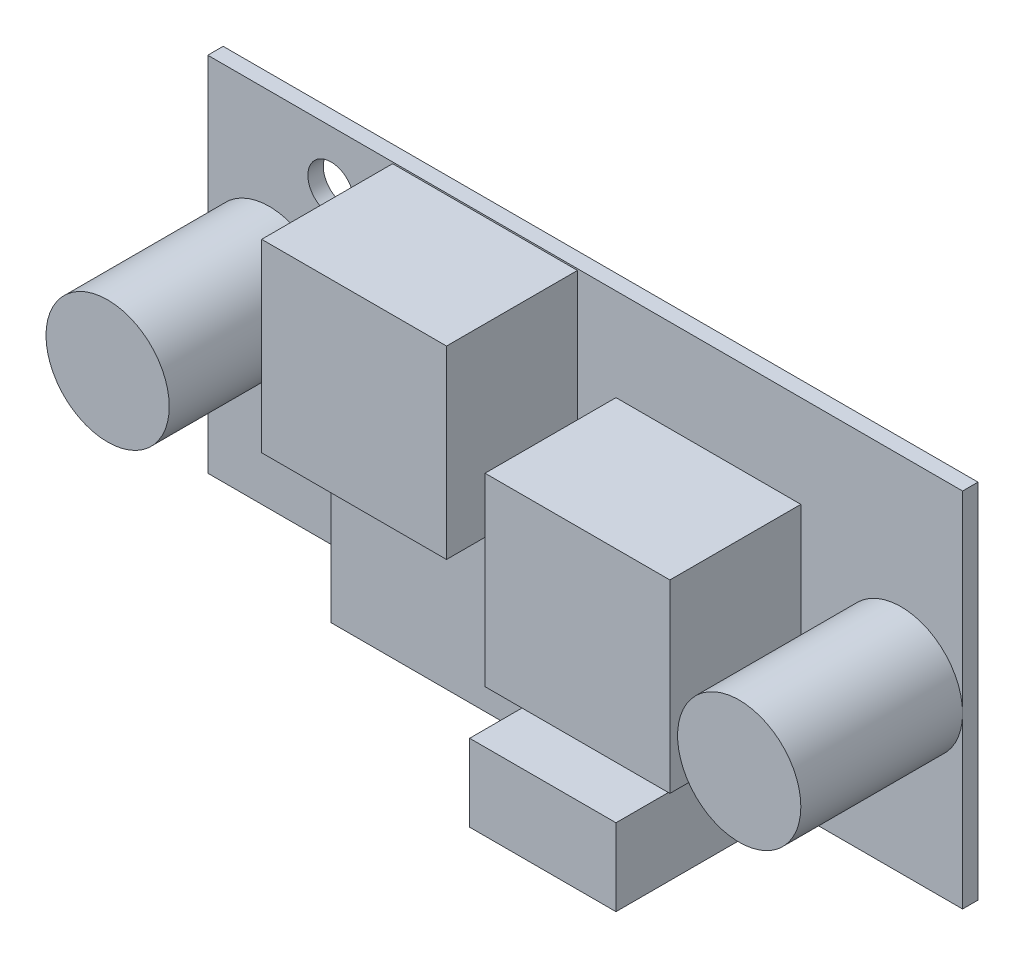
SolidWorks part; units mm, degrees
ref_plane "Спереди" through (0, 0, 0) normal (0, 0, 1) x (1, 0, 0)
ref_plane "Сверху" through (0, 0, 0) normal (0, 1, 0) x (1, 0, 0)
ref_plane "Справа" through (0, 0, 0) normal (1, 0, 0) x (0, 0, -1)
sketch "Эскиз1" plane through (0, 0, 0) normal (0, 0, 1) x (1, 0, 0)
  line L0 (0, 0) -> (-16.5, 8.25) construction
  line L1 (-24.5, 11.75) -> (24.5, 11.75)
  line L2 (-24.5, 11.75) -> (-24.5, -11.75)
  line L3 (-24.5, -11.75) -> (24.5, -11.75)
  line L4 (24.5, 11.75) -> (24.5, -11.75)
  line L5 (-24.5, 11.75) -> (24.5, -11.75) construction
  line L6 (-24.5, -11.75) -> (24.5, 11.75) construction
  circle A1 centre (-16.5, 8.25) radius 1.5
  circle A2 centre (16.5, -8.25) radius 1.5
  point P0 (0, 0)
  dimension "D1" = 49
  dimension "D3" = 3
  dimension "D2" = 23.5
  dimension "D4" = 8
  dimension "D5" = 3.5
extrude "Плата-основа" add sketch "Эскиз1" along normal blind 1
sketch "Эскиз2" plane through (0, 0, 1) normal (0, 0, 1) x (1, 0, 0)
  line L0 (-24.5, 11.75) -> (-24.5, -11.75) construction
  line L1 (-12.5, 11.65) -> (-0.5, 11.65)
  line L2 (-12.5, 11.65) -> (-12.5, -0.35)
  line L3 (-12.5, -0.35) -> (-0.5, -0.35)
  line L4 (-0.5, 11.65) -> (-0.5, -0.35)
  line L5 (-12.5, 11.65) -> (-0.5, -0.35) construction
  line L6 (-12.5, -0.35) -> (-0.5, 11.65) construction
  line L7 (4, -6.65) -> (13.5, -6.65)
  line L8 (4, -6.65) -> (4, -11.65)
  line L9 (4, -11.65) -> (13.5, -11.65)
  line L10 (13.5, -6.65) -> (13.5, -11.65)
  line L11 (4, -6.65) -> (13.5, -11.65) construction
  line L12 (4, -11.65) -> (13.5, -6.65) construction
  line L13 (2, 5.75) -> (14, 5.75)
  line L14 (2, 5.75) -> (2, -6.25)
  line L15 (2, -6.25) -> (14, -6.25)
  line L16 (14, 5.75) -> (14, -6.25)
  line L17 (2, 5.75) -> (14, -6.25) construction
  line L18 (2, -6.25) -> (14, 5.75) construction
  line L19 (24.5, 11.75) -> (-24.5, 11.75) construction
  line L20 (-24.5, -11.75) -> (24.5, -11.75) construction
  line L21 (24.5, -11.75) -> (24.5, 11.75) construction
  line L23 (-12, -1.65) -> (1, -1.65)
  line L24 (-12, -1.65) -> (-12, -11.65)
  line L25 (-12, -11.65) -> (1, -11.65)
  line L26 (1, -1.65) -> (1, -11.65)
  line L27 (-12, -1.65) -> (1, -11.65) construction
  line L28 (-12, -11.65) -> (1, -1.65) construction
  circle A0 centre (-20.5, 1.25) radius 4
  circle A1 centre (20.5, -0.75) radius 4
  point P2 (-6.5, 5.65)
  point P7 (8.75, -9.15)
  point P12 (8, -0.25)
  point P21 (-5.5, -6.65)
  point P32 (8.75, -8.5524)
  point P33 (-5.5, -5.6443)
  point P34 (-6.5, 5.1995)
  line M8 (24.5, 11.75) -> (-24.5, 11.75)
  line M10 (-24.5, -11.75) -> (24.5, -11.75)
  dimension "D1" = 8
  dimension "D2" = 10.5
  dimension "D3" = 12
  dimension "D4" = 9.5
  dimension "D5" = 5
  dimension "D6" = 11
  dimension "D7" = 11
  dimension "D8" = 12
  dimension "D9" = 10.5
  dimension "D10" = 6
  dimension "D11" = 10
  dimension "D12" = 13
  dimension "D13" = 12.5
  dimension "D14" = 0.1
  dimension "D15" = 0.1
extrude "Конденсаторы" add sketch "Эскиз2" along normal blind 10.5 contours A0 | A1 | A0 | A1 region at (-20.5, 1.25, 1) region at (20.5, -0.75, 1)
extrude "Регулятор" add sketch "Эскиз2<3>" along normal blind 11.5 contours L10 L7 L8 M10 region at (8.75, -9.15, 1)
sketch "Эскиз2<3>" plane through (0, 0, 1) normal (0, 0, 1) x (1, 0, 0) same geometry as "Эскиз2"
extrude "Какая то штука" add sketch "Эскиз2<5>" along normal blind 8.5 contours L4 L2 L3 M8 | L16 L13 L14 L15 region at (-6.5, 5.65, 1) region at (8, -0.25, 1)
sketch "Эскиз2<5>" plane through (0, 0, 1) normal (0, 0, 1) x (1, 0, 0) same geometry as "Эскиз2"
extrude "Микросхема" add sketch "Эскиз2<6>" along normal blind 4.5 contours L26 L23 L24 M10 region at (-5.5, -6.65, 1)
sketch "Эскиз2<6>" plane through (0, 0, 1) normal (0, 0, 1) x (1, 0, 0) same geometry as "Эскиз2"
